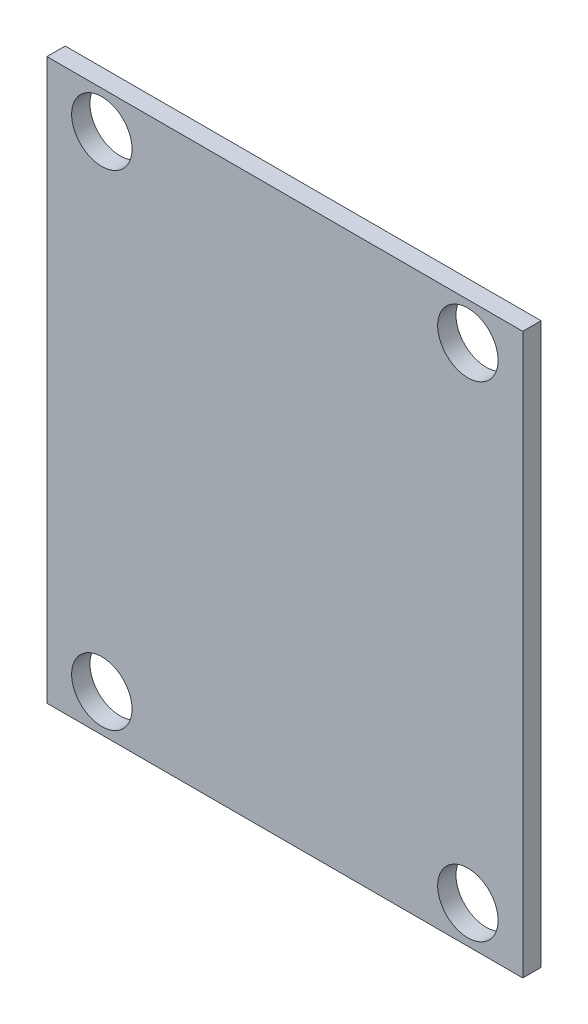
SolidWorks part; units mm, degrees
ref_plane "Front Plane" through (0, 0, 0) normal (0, 0, 1) x (1, 0, 0)
ref_plane "Top Plane" through (0, 0, 0) normal (0, 1, 0) x (1, 0, 0)
ref_plane "Right Plane" through (0, 0, 0) normal (1, 0, 0) x (0, 0, -1)
sketch "Sketch1" plane through (0, 0, 0) normal (0, 0, 1) x (1, 0, 0)
  line L1 (26, -30.6) -> (-26, -30.6)
  line L2 (26, -30.6) -> (26, 30.6)
  line L3 (26, 30.6) -> (-26, 30.6)
  line L4 (-26, -30.6) -> (-26, 30.6)
extrude "Boss-Extrude1" add sketch "Sketch1" along normal blind 2
hole_wizard "M6 Clearance Hole1" positions "Sketch2" profile "Sketch3" hole size "M6" standard "ISO" end condition through all
sketch "Sketch2" plane through (0, 0, 2) normal (0, 0, 1) x (1, 0, 0)
  point P2 (20, -26.5)
  point P5 (-20, -26.5)
  point P8 (-20, 26.5)
  point P11 (20, 26.5)
sketch "Sketch3" plane through (20, -26.5, 2) normal (1, 0, 0) x (0, -1, 0)
  line L0 (0, 0) -> (0, 2)
  line L1 (0, 2) -> (3.3, 2)
  line L2 (3.3, 2) -> (3.3, 0)
  line L5 (3.3, 0) -> (0, 0)
  line L11 (0, -6.35) -> (0, 107.95) construction
  dimension "Thru Hole Dia." = 6.6
  dimension "Thru Hole Depth" = 2
